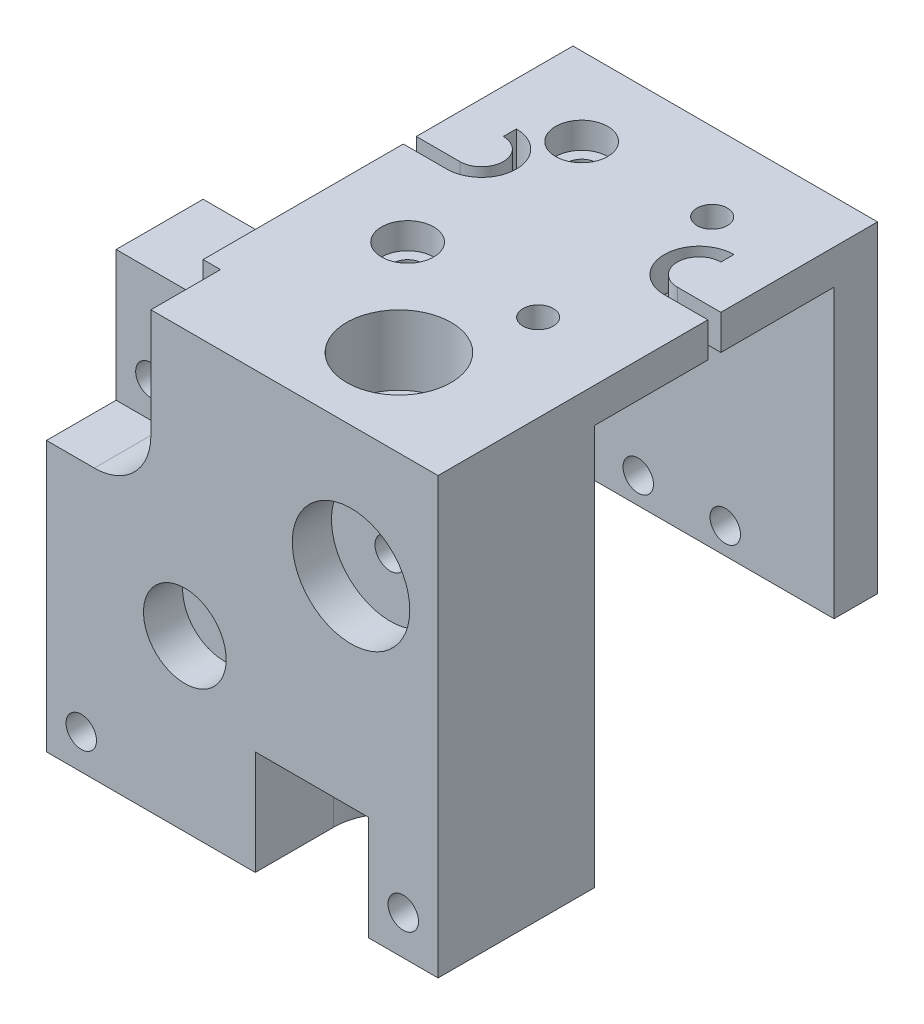
SolidWorks part; units mm, degrees
material "ABS"
ref_plane "Front Plane" through (0, 0, 0) normal (0, 0, 1) x (1, 0, 0)
ref_plane "Top Plane" through (0, 0, 0) normal (0, 1, 0) x (1, 0, 0)
ref_plane "Right Plane" through (0, 0, 0) normal (1, 0, 0) x (0, 0, -1)
sketch "Sketch1" plane through (0, 0, 0) normal (0, 1, 0) x (1, 0, 0)
  line L1 (-17.5, -14) -> (17.5, -14)
  line L2 (-17.5, -14) -> (-17.5, 14)
  line L3 (-17.5, 14) -> (17.5, 14)
  line L4 (17.5, -14) -> (17.5, 14)
  line L5 (-17.5, -14) -> (17.5, 14) construction
  line L6 (-17.5, 14) -> (17.5, -14) construction
  point P0 (0, 0)
  dimension "D1" = 28
  dimension "D2" = 35
extrude "Boss-Extrude1" add sketch "Sketch1" along normal blind 4
sketch "Sketch2" plane through (0, 4, 0) normal (0, 1, 0) x (1, 0, 0)
  line L0 (-17.5, -14) -> (17.5, -14) construction
  line L1 (-17.5, 14) -> (-17.5, -14) construction
  line L2 (-17.5, -14) -> (17.5, -14) construction
  line L3 (17.5, 14) -> (-17.5, 14) construction
  circle A0 centre (-7.5, -10) radius 1.75
  circle A1 centre (-7.5, 10) radius 1.75
  circle A2 centre (7.5, -10) radius 1.75
  circle A3 centre (7.5, 10) radius 1.75
  dimension "D1" = 3.5
  dimension "D2" = 3.5
  dimension "D5" = 3.5
  dimension "D8" = 3.5
  dimension "D3" = 20
  dimension "D4" = 4
  dimension "D6" = 15
  dimension "D7" = 10
  dimension "D9" = 15
  dimension "D10" = 4
  dimension "D11" = 4
extrude "Cut-Extrude1" cut sketch "Sketch2" against normal through all
sketch "Sketch3" plane through (0, 0, 14) normal (0, 0, 1) x (1, 0, 0)
  line L0 (17.5, 4) -> (17.5, 0) construction
  line L1 (-17.5, 4) -> (17.5, 4)
  line L2 (-17.5, 4) -> (-17.5, -46)
  line L3 (-17.5, -46) -> (17.5, -46)
  line L4 (17.5, 4) -> (17.5, -46)
  dimension "D1" = 50
extrude "Boss-Extrude2" add sketch "Sketch3" along normal blind 17.5 and the other way blind 0.5
sketch "Sketch7" plane through (0, 0, -14) normal (0, 0, -1) x (-1, 0, 0)
  line L1 (-17.5, 4) -> (17.5, 4)
  line L2 (-17.5, 4) -> (-17.5, -33)
  line L3 (-17.5, -33) -> (17.5, -33)
  line L4 (17.5, 4) -> (17.5, -33)
  line L6 (17.5, 4) -> (17.5, 0) construction
  dimension "D1" = 37
extrude "Boss-Extrude3" add sketch "Sketch7" along normal blind 5
sketch "Sketch10" plane through (0, 0, -19) normal (0, 0, -1) x (-1, 0, 0)
  line L1 (0, 4) -> (0, -33) construction
  line L3 (17.5, 4) -> (-17.5, 4) construction
  line L4 (-17.5, -33) -> (17.5, -33) construction
  circle A1 centre (-5, -30) radius 1.75
  circle A2 centre (5, -30) radius 1.75
  dimension "D1" = 3
  dimension "D2" = 3.5
  dimension "D4" = 3.5
  dimension "D3" = 5
  dimension "D5" = 5
extrude "Cut-Extrude6" cut sketch "Sketch10" against normal blind 5
sketch "Sketch18" plane through (0, 4, 0) normal (0, 1, 0) x (1, 0, 0)
  line L0 (-17.5, -10) -> (-10.5, -10)
  line L1 (-17.5, 19) -> (-17.5, -31.5) construction
  line L2 (-10.5, -10) -> (-10.5, -11.5)
  line L3 (-10.5, -11.5) -> (-17.5, -11.5)
  line L4 (-17.5, -11.5) -> (-17.5, -10)
  line L5 (17.5, 10) -> (10.5, 10)
  line L6 (17.5, -31.5) -> (17.5, 19) construction
  line L7 (10.5, 10) -> (10.5, 11.5)
  line L8 (10.5, 11.5) -> (17.5, 11.5)
  line L9 (17.5, 11.5) -> (17.5, 10)
  circle A0 centre (-7.5, -10) radius 1.75 construction
  circle A1 centre (7.5, 10) radius 1.75 construction
  dimension "D4" = 3
  dimension "D1" = 0
  dimension "D2" = 3
  dimension "D3" = 1.5
  dimension "D5" = 0
  dimension "D6" = 1.5
extrude "Cut-Extrude14" [suppressed] cut sketch "Sketch18" against normal through all
sketch "Sketch19" plane through (0, 4, 0) normal (0, 1, 0) x (1, 0, 0)
  line L0 (-17.5, 19) -> (-17.5, -31.5) construction
  line L1 (17.5, -31.5) -> (17.5, 19) construction
  circle A0 centre (-7.5, 0) radius 1.75
  circle A1 centre (7.5, 0) radius 1.75
  dimension "D3" = 3.5
  dimension "D4" = 3.5
  dimension "D1" = 10
  dimension "D2" = 10
extrude "Cut-Extrude15" [suppressed] cut sketch "Sketch19" against normal through all
sketch "Sketch20" [suppressed] plane through (0, 0, 0) normal (0, -1, 0) x (1, 0, 0)
  line L1 (10.9641, 0) -> (9.2321, 3)
  line L2 (9.2321, 3) -> (5.7679, 3)
  line L3 (5.7679, 3) -> (4.0359, 0)
  line L4 (4.0359, 0) -> (5.7679, -3)
  line L5 (5.7679, -3) -> (9.2321, -3)
  line L6 (9.2321, -3) -> (10.9641, 0)
  line L7 (-10.9641, 0) -> (-9.2321, -3)
  line L8 (-9.2321, -3) -> (-5.7679, -3)
  line L9 (-5.7679, -3) -> (-4.0359, 0)
  line L10 (-4.0359, 0) -> (-5.7679, 3)
  line L11 (-5.7679, 3) -> (-9.2321, 3)
  line L12 (-9.2321, 3) -> (-10.9641, 0)
  circle A0 centre (7.5, 0) radius 3 construction
  circle A1 centre (-7.5, 0) radius 3 construction
  dimension "D1" = 6
  dimension "D2" = 6
extrude "Cut-Extrude16" [suppressed] cut sketch "Sketch20" against normal blind 3
sketch "Sketch21" [suppressed] plane through (0, 4, 0) normal (0, 1, 0) x (1, 0, 0)
  line L0 (-10.5, -10) -> (-17.5, -10) construction
  circle A0 centre (-17, -10) radius 0.5
  dimension "D1" = 1
extrude "Cut-Extrude17" [suppressed] cut sketch "Sketch21" against normal blind 4
pattern_linear "LPattern2" [suppressed] count 4 spacing 2 of bodies 121
fillet "Fillet2" [suppressed] radius 0.15
sketch "Sketch24" plane through (-17.5, 0, 0) normal (-1, 0, 0) x (0, 0, 1)
  line L5 (31.5, -46) -> (13.5, -46) construction
  line L6 (13.5, -46) -> (31.5, -46)
  line L7 (13.5, -46) -> (13.5, 0)
  line L8 (13.5, 0) -> (31.5, 0)
  line L9 (31.5, -46) -> (31.5, 0)
  line L10 (13.5, 0) -> (13.5, -46) construction
  line L11 (31.5, 4) -> (31.5, -46) construction
extrude "Boss-Extrude4" add sketch "Sketch24" along normal blind 10
sketch "Sketch22" plane through (0, 0, 31.5) normal (0, 0, 1) x (1, 0, 0)
  line L0 (-27.5, -46) -> (-27.5, 0) construction
  line L1 (-15.5, 0) -> (-27.5, 0)
  line L2 (-27.5, -46) -> (17.5, -46) construction
  line L4 (-27.5, 0) -> (-17.5, 0) construction
  line L5 (-27.5, -46) -> (17.5, -46) construction
  line L6 (-27.5, 0) -> (-27.5, -15)
  line L9 (-27.5, -15) -> (-22, -15)
  line L10 (-15.5, 0) -> (-15.5, -8.5)
  line L11 (9.5, -46) -> (-3.5, -46)
  line L12 (9.5, -46) -> (9.5, -34)
  line L13 (9.5, -34) -> (-3.5, -34)
  line L14 (-3.5, -46) -> (-3.5, -34)
  line L16 (-15.5, 0) -> (-17.5, 0)
  line L17 (-15.5, 0) -> (-15.5, 4)
  line L18 (-15.5, 4) -> (-17.5, 4)
  line L19 (-17.5, 0) -> (-17.5, 4)
  circle A0 centre (-23.5, -42) radius 1.75
  circle A1 centre (13.5, -41.5) radius 1.75
  circle A3 centre (7.5, -11) radius 6.75
  circle A4 centre (-11.6, -26.5) radius 4.75
  arc A5 (-22, -15) -> (-15.5, -8.5) centre (-22, -8.5) ccw
  circle A6 centre (7.5, -11) radius 1.75
  circle A7 centre (-23.5, -11) radius 1.75
  point P21 (-15.5, -15)
  line M3 (-17.5, 4) -> (-17.5, 0)
  line M6 (17.5, 4) -> (-17.5, 4)
  line M24 (-17.5, 0) -> (-27.5, 0)
  line M25 (-27.5, 0) -> (-27.5, -46)
  dimension "D3" = 3.5
  dimension "D6" = 35
  dimension "D7" = 3.5
  dimension "D9" = 13.5
  dimension "D11" = 9.5
  dimension "D15" = 6.5
  dimension "D22" = 3.5
  dimension "D23" = 3.5
  dimension "D2" = 4
  dimension "D4" = 4.5
  dimension "D5" = 4
  dimension "D8" = 12
  dimension "D10" = 35
  dimension "D12" = 15.9
  dimension "D13" = 19.5
  dimension "D14" = 31
  dimension "D16" = 24
  dimension "D17" = 13
  dimension "D18" = 12
  dimension "D19" = 41
  dimension "D20" = 4
  dimension "D21" = 35
extrude "Cut-Extrude19" cut sketch "Sketch22" against normal up to next contours A0 | A1 | A7 | A6 region at (-23.5, -42, 31.5) region at (13.5, -41.5, 31.5) region at (7.5, -11, 31.5) region at (-23.5, -11, 31.5)
extrude "Cut-Extrude20" cut sketch "Sketch22<3>" against normal blind 4.5 contours A3 | A4
sketch "Sketch22<3>" plane through (0, 0, 31.5) normal (0, 0, 1) x (1, 0, 0) same geometry as "Sketch22"
extrude "Cut-Extrude24" cut sketch "Sketch22<5>" against normal blind 8 contours L9 A5 L10 L1 A7 M24 M25 | L1 L17 M6 M3 region at (-21.6364, -6.9513, 31.5) region at (-16.5, 2, 31.5)
sketch "Sketch22<5>" plane through (0, 0, 31.5) normal (0, 0, 1) x (1, 0, 0) same geometry as "Sketch22"
extrude "Cut-Extrude21" cut sketch "Sketch22<4>" against normal blind 15.5 contours L14 L13 L12 L11
sketch "Sketch22<4>" plane through (0, 0, 31.5) normal (0, 0, 1) x (1, 0, 0) same geometry as "Sketch22"
fillet "Fillet3" radius 6.5 2 edges at (9.5, -40, 16) (-3.5, -40, 16)
sketch "Sketch26" plane through (0, -34, 0) normal (0, -1, 0) x (1, 0, 0)
  line L0 (9.5, 31.5) -> (-3.5, 31.5) construction
  line L1 (-3.5, 22.5) -> (-3.5, 31.5) construction
  circle A0 centre (3, 21.5) radius 2.25
  dimension "D1" = 4.5
  dimension "D2" = 10
  dimension "D3" = 6.5
extrude "Cut-Extrude22" cut sketch "Sketch26" against normal through all
sketch "Sketch27" plane through (0, 4, 0) normal (0, 1, 0) x (1, 0, 0)
  circle A0 centre (3, -21.5) radius 6
  dimension "D1" = 12
extrude "Cut-Extrude23" cut sketch "Sketch27" against normal blind 8
sketch "Sketch29" plane through (0, 0, 13.5) normal (0, 0, -1) x (-1, 0, 0)
  line L1 (-4.0359, -11) -> (-5.7679, -8)
  line L2 (-5.7679, -8) -> (-9.2321, -8)
  line L3 (-9.2321, -8) -> (-10.9641, -11)
  line L4 (-10.9641, -11) -> (-9.2321, -14)
  line L5 (-9.2321, -14) -> (-5.7679, -14)
  line L6 (-5.7679, -14) -> (-4.0359, -11)
  line L7 (20.0359, -11) -> (21.7679, -14)
  line L8 (21.7679, -14) -> (25.2321, -14)
  line L9 (25.2321, -14) -> (26.9641, -11)
  line L10 (26.9641, -11) -> (25.2321, -8)
  line L11 (25.2321, -8) -> (21.7679, -8)
  line L12 (21.7679, -8) -> (20.0359, -11)
  line L13 (-10.0359, -41.5) -> (-11.7679, -38.5)
  line L14 (-11.7679, -38.5) -> (-15.2321, -38.5)
  line L15 (-15.2321, -38.5) -> (-16.9641, -41.5)
  line L16 (-16.9641, -41.5) -> (-15.2321, -44.5)
  line L17 (-15.2321, -44.5) -> (-11.7679, -44.5)
  line L18 (-11.7679, -44.5) -> (-10.0359, -41.5)
  line L19 (20.0359, -42) -> (21.7679, -45)
  line L20 (21.7679, -45) -> (25.2321, -45)
  line L21 (25.2321, -45) -> (26.9641, -42)
  line L22 (26.9641, -42) -> (25.2321, -39)
  line L23 (25.2321, -39) -> (21.7679, -39)
  line L24 (21.7679, -39) -> (20.0359, -42)
  circle A0 centre (-7.5, -11) radius 3 construction
  circle A1 centre (23.5, -11) radius 3 construction
  circle A2 centre (-13.5, -41.5) radius 3 construction
  circle A3 centre (23.5, -42) radius 3 construction
  dimension "D1" = 6
  dimension "D2" = 6
  dimension "D3" = 6
  dimension "D4" = 6
extrude "Cut-Extrude25" cut sketch "Sketch29" against normal blind 2
sketch "Sketch30" plane through (0, 4, 0) normal (0, 1, 0) x (1, 0, 0)
  circle A0 centre (-7.5, 10) radius 3
  circle A1 centre (-7.5, -10) radius 3
  dimension "D1" = 6
  dimension "D2" = 6
extrude "Cut-Extrude26" cut sketch "Sketch30" against normal blind 3
sketch "Sketch31" plane through (0, 4, 0) normal (0, 1, 0) x (1, 0, 0)
  line L0 (-17.5, 0) -> (17.5, 0) construction
  line L1 (-17.5, 19) -> (-17.5, -23.5) construction
  line L2 (17.5, -31.5) -> (17.5, 19) construction
  line L4 (-17.5, 1) -> (-12.5, 1)
  line L10 (-17.5, -0.5) -> (-12.5, -0.5)
  line L11 (-17.5, 1) -> (-17.5, -0.5)
  line L12 (-12.5, 6) -> (-12.5, 7.5)
  arc A0 (-12.5, 1) -> (-12.5, 6) centre (-12.5, 3.5) ccw
  arc A2 (-12.5, -0.5) -> (-12.5, 7.5) centre (-12.5, 3.5) ccw
  dimension "D4" = 2.5
  dimension "D1" = 1
  dimension "D2" = 1.5
  dimension "D3" = 5
extrude "Cut-Extrude27" cut sketch "Sketch31" against normal through all
ref_plane "Plane1" through (0, 0, 0) normal (-1, 0, 0) x (0, 0, 1)
mirror "Mirror1" about plane through (0, 0, 0) normal (-1, 0, 0) of "Cut-Extrude27"
